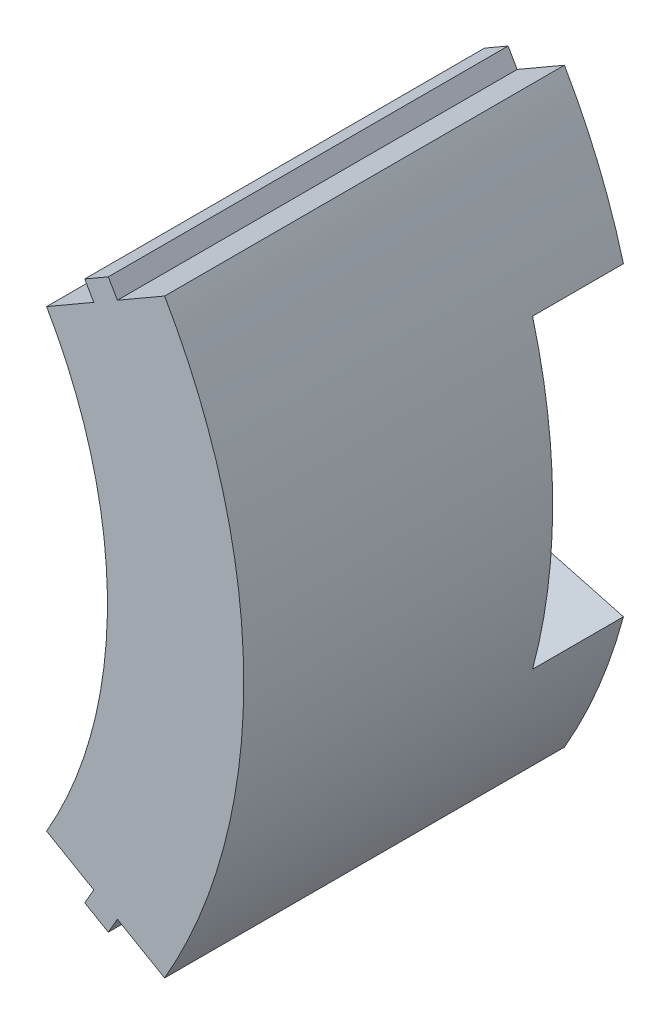
SolidWorks part; units mm, degrees
ref_plane "Спереди" through (0, 0, 0) normal (0, 0, 1) x (1, 0, 0)
ref_plane "Сверху" through (0, 0, 0) normal (0, 1, 0) x (1, 0, 0)
ref_plane "Справа" through (0, 0, 0) normal (1, 0, 0) x (0, 0, -1)
sketch "Эскиз1" plane through (0, 0, 0) normal (0, 0, 1) x (1, 0, 0)
  line L0 (0, 0) -> (0, 57.8819) construction
  line L1 (0, 0) -> (171.1762, 0) construction
  line L2 (0, 0) -> (145.7194, 84.1311) construction
  line L3 (21.6506, 12.5) -> (28.1458, 16.25)
  line L4 (21.6506, -12.5) -> (28.1458, -16.25)
  arc A0 (21.6506, -12.5) -> (21.6506, 12.5) centre (0, 0) ccw
  arc A1 (28.1458, -16.25) -> (28.1458, 16.25) centre (0, 0) ccw
  dimension "D2" = 65
  dimension "D3" = 50
  dimension "D1" = 30
extrude "Бобышка-Вытянуть1" add sketch "Эскиз1" along normal blind 22
sketch "Эскиз2" plane through (0, 0, 0) normal (-0.5, -0.866, 0) x (0.866, -0.5, 0)
  line L0 (28.75, 22) -> (28.75, 0) construction
  line L1 (25, 22) -> (32.5, 22) construction
  line L2 (25, 0) -> (32.5, 0) construction
  line L3 (28, 22) -> (29.5, 22)
  line L4 (29.5, 22) -> (29.5, 0)
  line L5 (29.5, 0) -> (28, 0)
  line L6 (28, 22) -> (28, 0)
  dimension "D1" = 0.75
sketch "Эскиз4" plane through (0, 0, 0) normal (-0.5, 0.866, 0) x (-0.866, -0.5, 0)
  line L0 (-28.75, 22) -> (-28.75, 0) construction
  line L3 (-29.5, 22) -> (-28, 22)
  line L4 (-28, 22) -> (-28, 0)
  line L5 (-28, 0) -> (-29.5, 0)
  line L6 (-29.5, 22) -> (-29.5, 0)
  line L7 (-32.5, 22) -> (-25, 22) construction
  line L8 (-32.5, 0) -> (-25, 0) construction
  point P2 (0, 0)
  point P3 (-28.75, 22)
  point P4 (-28.75, 0)
  point P11 (0, 0)
  point P14 (0, 0)
  point P15 (0, 0)
  dimension "D1" = 0.75
extrude "Бобышка-Вытянуть2" add sketch "Эскиз4" along normal blind 1 contours L6 L5 L4 L3
extrude "Бобышка-Вытянуть3" add sketch "Эскиз2" along normal blind 1 contours L6 L5 L4 L3
sketch "Эскиз6" plane through (0, 0, 0) normal (0, 0, -1) x (-1, 0, 0)
  line L0 (0, 0) -> (-46.585, 0) construction
  line L1 (0, 0) -> (-46.0133, 12.3292) construction
  line L2 (-24.1481, 6.4705) -> (-31.3926, 8.4116)
  line L3 (-24.1481, -6.4705) -> (-31.3926, -8.4116)
  arc A0 (-31.3926, 8.4116) -> (-31.3926, -8.4116) centre (0, 0) ccw
  arc A1 (-28.1458, 16.25) -> (-28.1458, -16.25) centre (0, 0) ccw construction
  arc A2 (-24.1481, 6.4705) -> (-24.1481, -6.4705) centre (0, 0) ccw
  arc A3 (-21.6506, 12.5) -> (-21.6506, -12.5) centre (0, 0) ccw construction
  dimension "D1" = 15
extrude "Вырез-Вытянуть2" cut sketch "Эскиз6" against normal blind 5
